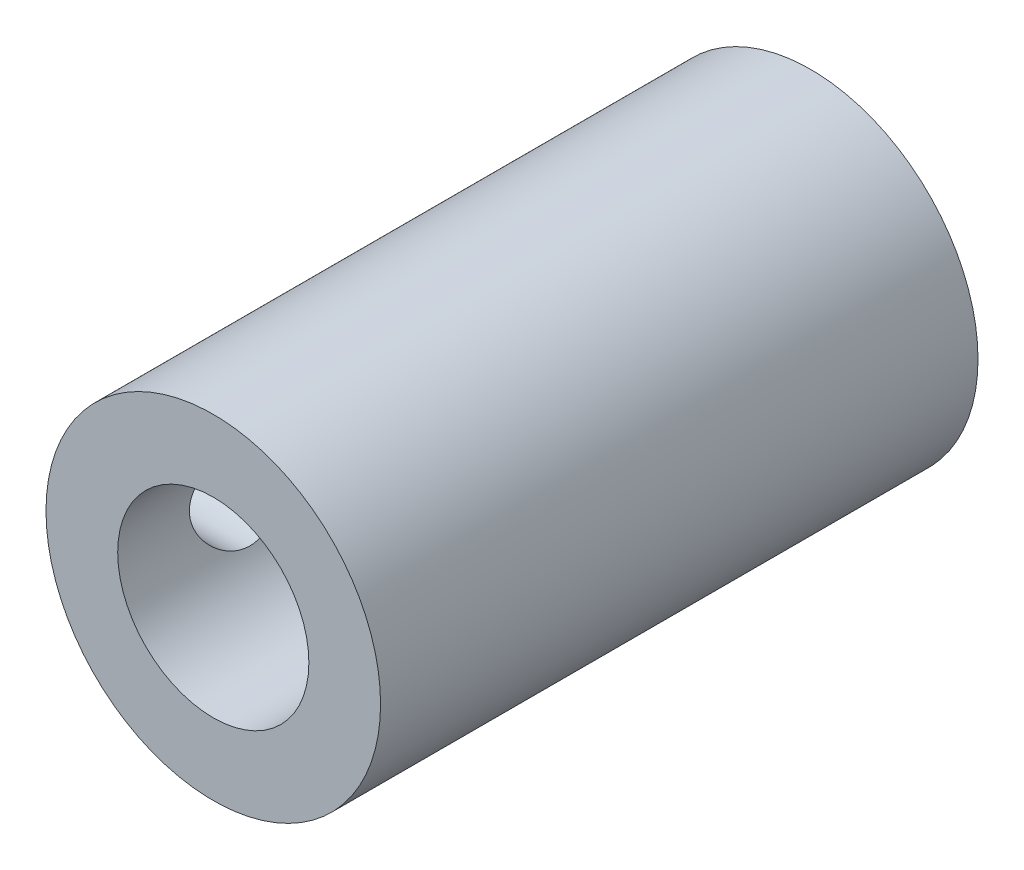
SolidWorks part; units mm, degrees
material "1060 Alloy"
ref_plane "Front Plane" through (0, 0, 0) normal (1, 0, 0) x (0, 1, 0)
ref_plane "Top Plane" through (0, 0, 0) normal (0, 0, 1) x (0, 1, 0)
ref_plane "Right Plane" through (0, 0, 0) normal (0, 1, 0) x (-1, 0, 0)
sketch "Sketch1" plane through (0, 0, 0) normal (0, 0, 1) x (0, 1, 0)
  circle A0 centre (0, 0) radius 7
  circle A1 centre (0, 0) radius 3
  dimension "D1" = 6
  dimension "D2" = 14
extrude "Boss-Extrude1" add sketch "Sketch1" along normal blind 25
sketch "Sketch2" plane through (0, 0, 25) normal (0, 0, 1) x (1, 0, 0)
  circle A3 centre (0, 0) radius 4
  dimension "D1" = 8
extrude "Cut-Extrude1" cut sketch "Sketch2" against normal blind 13
sketch "Sketch3" plane through (0, 0, 0) normal (1, 0, 0) x (0, 1, 0)
  line L0 (4, 25) -> (-4, 25) construction
  circle A0 centre (0, 5) radius 2
  circle A1 centre (0, 20) radius 2
  dimension "D1" = 5
  dimension "D2" = 5
  dimension "D3" = 4
  dimension "D4" = 4
extrude "Cut-Extrude2" cut sketch "Sketch3" against normal blind 12
ref_plane "Plane1" through (-7, 0, 0) normal (-1, 0, 0) x (0, 0, 1)
sketch "Sketch5" plane through (-7, 0, 0) normal (-1, 0, 0) x (0, 0, 1)
  circle A0 centre (5, 0) radius 2.5156
extrude "Cut-Extrude3" cut sketch "Sketch5" against normal blind 1
